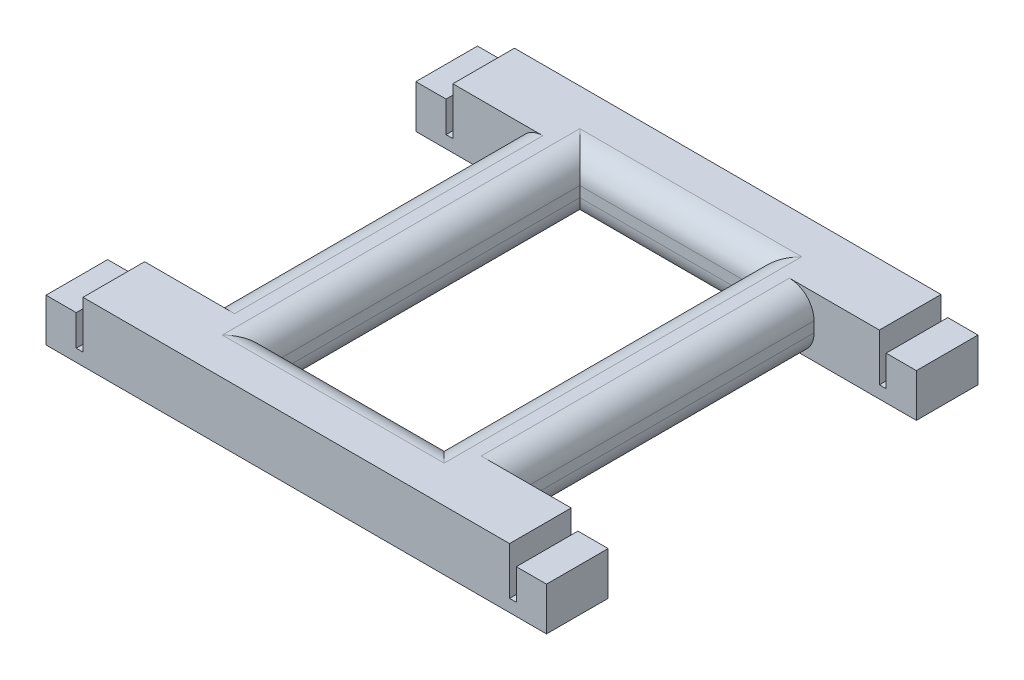
SolidWorks part; units mm, degrees
ref_plane "Front Plane" through (0, 0, 0) normal (0, 0, 1) x (1, 0, 0)
ref_plane "Top Plane" through (0, 0, 0) normal (0, 1, 0) x (1, 0, 0)
ref_plane "Right Plane" through (0, 0, 0) normal (1, 0, 0) x (0, 0, -1)
ref_axis "X Axis" through (-39.3295, 0, 0) along (1, 0, 0)
ref_axis "Y Axis" through (0, 0, -37.7472) along (0, 0, 1)
ref_axis "Z Axis" through (0, 35.6627, 0) along (0, -1, 0)
sketch "Sketch1" plane through (0, 0, 0) normal (0, 1, 0) x (1, 0, 0)
  line L0 (0, 75) -> (0, -75) construction
  line L1 (-60, 62.5) -> (-60, -62.5)
  line L2 (-86.5, 62.5) -> (-60, 62.5)
  line L3 (-86.5, 62.5) -> (-86.5, 87.5)
  line L4 (-86.5, 87.5) -> (86.5, 87.5)
  line L5 (86.5, 62.5) -> (86.5, 87.5)
  line L6 (-86.5, 62.5) -> (86.5, 87.5) construction
  line L7 (-86.5, 87.5) -> (86.5, 62.5) construction
  line L8 (-86.5, -87.5) -> (86.5, -87.5)
  line L9 (-86.5, -87.5) -> (-86.5, -62.5)
  line L10 (-86.5, -62.5) -> (-60, -62.5)
  line L11 (86.5, -87.5) -> (86.5, -62.5)
  line L12 (-86.5, -87.5) -> (86.5, -62.5) construction
  line L13 (-86.5, -62.5) -> (86.5, -87.5) construction
  line L14 (-35, 62.5) -> (-35, -62.5)
  line L15 (35, 62.5) -> (35, -62.5)
  line L16 (60, 62.5) -> (60, -62.5)
  line L17 (-60, 0) -> (60, 0) construction
  line L18 (-35, 62.5) -> (35, 62.5)
  line L19 (60, 62.5) -> (86.5, 62.5)
  line L20 (60, -62.5) -> (86.5, -62.5)
  line L21 (-35, -62.5) -> (35, -62.5)
  point P2 (0, 0)
  point P22 (0, 0)
  dimension "D1" = 150
  dimension "D2" = 173
  dimension "D3" = 25
  dimension "D4" = 25
  dimension "D5" = 25
  dimension "D6" = 120
extrude "Boss-Extrude1" add sketch "Sketch1" against normal blind 5 and the other way blind 19.25
sketch "Sketch2" plane through (0, -5, 0) normal (0, 1, 0) x (1, 0, 0)
  line L0 (86.5, -87.5) -> (86.5, -62.5) construction
  line L1 (-86.5, 87.5) -> (-101.5, 87.5)
  line L2 (-86.5, 87.5) -> (-86.5, 62.5)
  line L3 (-86.5, 62.5) -> (-101.5, 62.5)
  line L4 (-101.5, 87.5) -> (-101.5, 62.5)
  line L5 (86.5, 87.5) -> (101.5, 87.5)
  line L6 (86.5, 87.5) -> (86.5, 62.5)
  line L7 (86.5, 62.5) -> (101.5, 62.5)
  line L8 (101.5, 87.5) -> (101.5, 62.5)
  line L9 (-86.5, -62.5) -> (-101.5, -62.5)
  line L10 (-86.5, -62.5) -> (-86.5, -87.5)
  line L11 (-86.5, -87.5) -> (-101.5, -87.5)
  line L12 (-101.5, -62.5) -> (-101.5, -87.5)
  line L13 (86.5, -62.5) -> (101.5, -62.5)
  line L14 (86.5, -62.5) -> (86.5, -87.5)
  line L15 (86.5, -87.5) -> (101.5, -87.5)
  line L16 (101.5, -62.5) -> (101.5, -87.5)
  dimension "D1" = 15
extrude "Boss-Extrude2" add sketch "Sketch2" along normal up to surface (5 mm away) up to plane "Top Plane"
sketch "Sketch3" plane through (0, 0, 0) normal (0, 1, 0) x (1, 0, 0)
  line L0 (-101.5, 62.5) -> (-86.5, 62.5) construction
  line L1 (-101.5, 87.5) -> (-89.25, 87.5)
  line L2 (-101.5, 87.5) -> (-101.5, 62.5)
  line L3 (-101.5, 62.5) -> (-89.25, 62.5)
  line L4 (-89.25, 87.5) -> (-89.25, 62.5)
  line L5 (-86.5, 62.5) -> (-86.5, 87.5) construction
  line L6 (101.5, 87.5) -> (89.25, 87.5)
  line L7 (101.5, 87.5) -> (101.5, 62.5)
  line L8 (101.5, 62.5) -> (89.25, 62.5)
  line L9 (89.25, 87.5) -> (89.25, 62.5)
  line L10 (-101.5, -62.5) -> (-89.25, -62.5)
  line L11 (-101.5, -62.5) -> (-101.5, -87.5)
  line L12 (-101.5, -87.5) -> (-89.25, -87.5)
  line L13 (-89.25, -62.5) -> (-89.25, -87.5)
  line L14 (101.5, -62.5) -> (89.25, -62.5)
  line L15 (101.5, -62.5) -> (101.5, -87.5)
  line L16 (101.5, -87.5) -> (89.25, -87.5)
  line L17 (89.25, -62.5) -> (89.25, -87.5)
  dimension "D1" = 2.75
extrude "Boss-Extrude3" add sketch "Sketch3" along normal blind 12.5
fillet "Fillet1" radius 10 12 edges at (0, 19.25, 62.5) (60, 19.25, 0) (35, 19.25, 0) (-60, 19.25, 0) (-35, 19.25, 0) (0, 19.25, -62.5) (0, -5, 62.5) (-35, -5, 0) (0, -5, -62.5) (35, -5, 0) (60, -5, 0) (-60, -5, 0)
